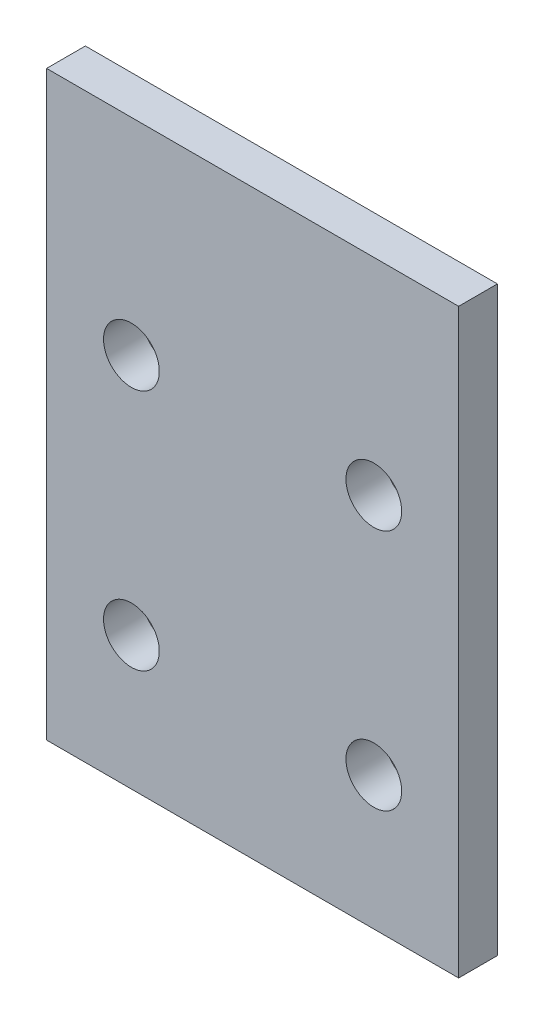
SolidWorks part; units mm, degrees
note: The reader was unsure of these and kept them because the rebuilt part matched: thickness of "Базовая кромка1", "Листовой металл1".
material "Простая углеродистая сталь"
ref_plane "Спереди" through (0, 0, 0) normal (0, 0, 1) x (1, 0, 0)
ref_plane "Сверху" through (0, 0, 0) normal (0, 1, 0) x (1, 0, 0)
ref_plane "Справа" through (0, 0, 0) normal (1, 0, 0) x (0, 0, -1)
sketch "Эскиз1" plane through (0, 0, 0) normal (0, 0, 1) x (1, 0, 0)
  line L1 (0, 0) -> (170, 0)
  line L2 (0, 0) -> (0, -240)
  line L3 (0, -240) -> (170, -240)
  line L4 (170, 0) -> (170, -240)
  line L5 (85, -240) -> (85, 0) construction
  line L6 (0, -120) -> (170, -120) construction
  circle A0 centre (135, -185) radius 11.5
  circle A1 centre (135, -85) radius 11.5
  circle A2 centre (35, -85) radius 11.5
  circle A3 centre (35, -185) radius 11.5
  point P96 (85, -120)
  dimension "D3" = 23
  dimension "D6" = 100
  dimension "D7" = 100
  dimension "D1" = 170
  dimension "D2" = 240
  dimension "D4" = 55
  dimension "D5" = 2
base flange "Базовая кромка1" sketch "Эскиз1" thickness 16 reverse thickness direction no parameters "D1"=1
sketch "Сгиб-Линии1" plane through (0, 0, 0) normal (0, 1, 0) x (1, 0, 0)
sketch "Граничная рамка1" plane through (0, 0, 0) normal (0, 1, 0) x (1, 0, 0)
sheet metal parameters "Листовой металл1" thickness 16 parameters "D1"=1, "D7"=4
flat pattern "Развертка1" [suppressed]
sketch "Сгиб-Линии2" plane through (0, 0, 0) normal (0, 1, 0) x (1, 0, 0)
sketch3d "Граничная рамка2" [suppressed]
  line L0 (170, 0, 0) -> (170, -240, 0) construction
  line L1 (0, 0, 0) -> (0, -240, 0) construction
  line L2 (170, 0, 0) -> (0, 0, 0) construction
  line L3 (170, -240, 0) -> (0, -240, 0) construction
